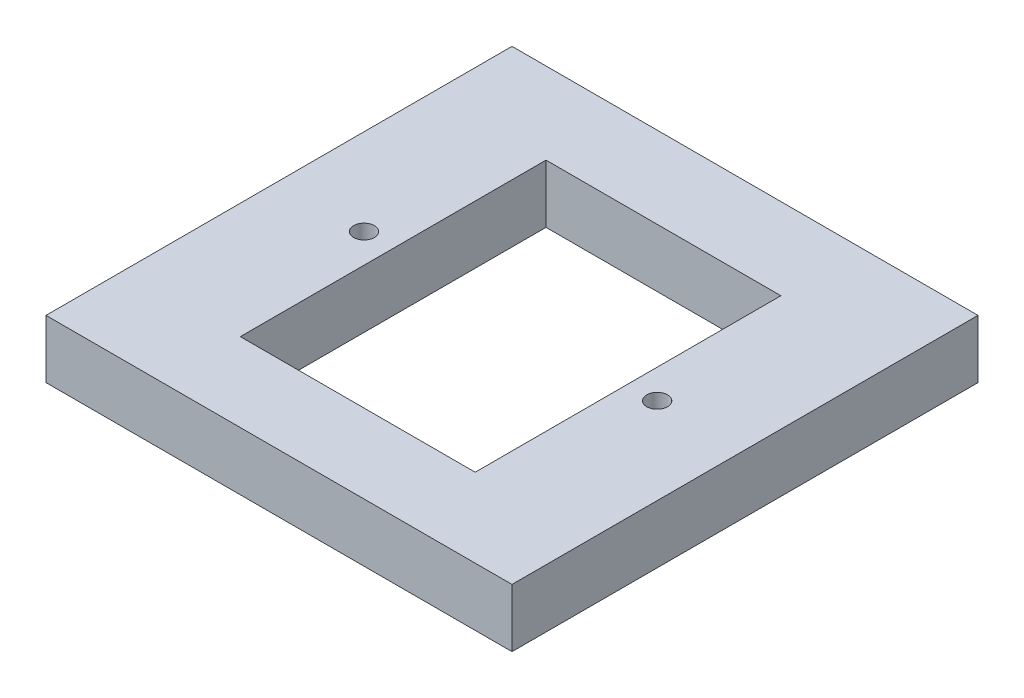
SolidWorks part; units mm, degrees
ref_plane "Front Plane" through (0, 0, 0) normal (0, 0, 1) x (1, 0, 0)
ref_plane "Top Plane" through (0, 0, 0) normal (0, 1, 0) x (1, 0, 0)
ref_plane "Right Plane" through (0, 0, 0) normal (1, 0, 0) x (0, 0, -1)
sketch "Sketch1" plane through (0, 0, 0) normal (0, 1, 0) x (1, 0, 0)
  line L0 (21.7665, 27.3408) -> (21.7665, -23.4592) construction
  line L1 (-3.6335, 27.3408) -> (47.1665, 27.3408)
  line L2 (-3.6335, 27.3408) -> (-3.6335, -23.4592)
  line L3 (-3.6335, -23.4592) -> (47.1665, -23.4592)
  line L4 (47.1665, 27.3408) -> (47.1665, -23.4592)
  line L6 (8.9649, 18.4508) -> (34.5681, 18.4508)
  line L7 (8.9649, 18.4508) -> (8.9649, -14.874)
  line L8 (8.9649, -14.874) -> (34.5681, -14.874)
  line L9 (34.5681, 18.4508) -> (34.5681, -14.874)
  circle A0 centre (37.7431, 1.7884) radius 1.1303
  circle A1 centre (5.7899, 1.7884) radius 1.1303
  dimension "D11" = 2.2606
  dimension "D12" = 2.2606
  dimension "D1" = 50.8
  dimension "D2" = 50.8
  dimension "D3" = 33.3248
  dimension "D4" = 25.6032
  dimension "D5" = 8.89
  dimension "D6" = 12.8016
  dimension "D7" = 3.175
  dimension "D8" = 3.175
  dimension "D9" = 16.6624
  dimension "D10" = 16.6624
extrude "Boss-Extrude1" add sketch "Sketch1" along normal blind 6.35
